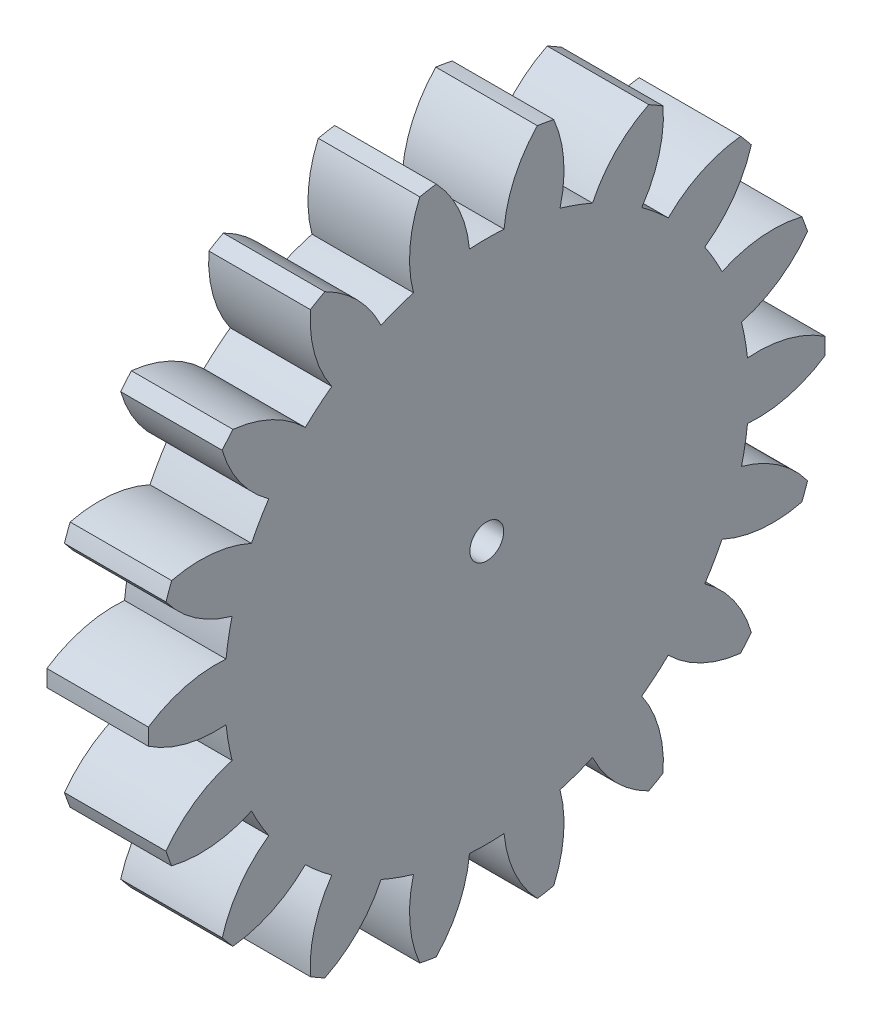
SolidWorks part; units mm, degrees
ref_plane "Plane1" through (0, 0, 0) normal (0, 0, 1) x (1, 0, 0)
ref_plane "Plane2" through (0, 0, 0) normal (0, 1, 0) x (1, 0, 0)
ref_plane "Plane3" through (0, 0, 0) normal (1, 0, 0) x (0, 0, -1)
sketch "HoldingSke" plane through (0, 0, 0) normal (0, 1, 0) x (1, 0, 0)
  line L0 (0, 0) -> (0.9511, -0.309)
  line L1 (-15, 0) -> (100, 0) construction
  line L2 (0, 0) -> (-2.1039, 2.3779)
  line L3 (0, 0) -> (-11.863, 4.5341)
  line L4 (0, 0) -> (8.2133, 2.6687)
  line L5 (0, 0) -> (-46.8476, -17.4728)
  line L6 (0, 0) -> (-2.4869, -1.6779)
  line L7 (-2.1039, 2.3779) -> (8.6586, 51.2059)
  line L8 (-76.2, 54.61) -> (-76.1, 54.61)
  line L9 (-71.009, 38.7566) -> (-53.1078, 45.2721)
  line L10 (-76.2, 71.12) -> (104.1128, 71.12)
  line L11 (0, 0) -> (-3, 0)
  line L12 (-76.2, 101.6) -> (-76.162, 101.6)
  line L13 (24.9733, 27.94) -> (52.9518, 28.4284)
  line L14 (24.9733, 27.94) -> (24.9743, 27.94)
  line L15 (24.9733, 27.94) -> (100.4006, 29.5858)
  line L16 (-63.627, -1) -> (-12.827, -1)
  circle A0 centre (0, 0) radius 0.5
  circle A1 centre (0, 0) radius 7.749
  circle A2 centre (0, 0) radius 37.5
  circle A3 centre (0, 0) radius 0.5
  dimension "Num_teeth" = 18
  dimension "Pitch_radius" = 180.3128
  dimension "Width" = 3
  dimension "Thickness" = 3
sketch "BasProSke" plane through (0, 0, 0) normal (0, 1, 0) x (1, 0, 0)
  line L0 (-10, 0) -> (60, 0) construction
  line L1 (0, 0) -> (0, 10)
  line L2 (0, 0) -> (3, 0)
  line L3 (3, 0) -> (3, 10)
  line L4 (3, 10) -> (0, 10)
  dimension "Thickness" = 3
  dimension "Diameter" = 20
revolve "Base-Revolve" add sketch "BasProSke" angle 360 about L0
sketch "TooCutSke" plane through (0, 0, 0) normal (1, 0, 0) x (0, 0, -1)
  line L1 (0, 0) -> (0, 107) construction
  line L2 (0, 0) -> (-0.8509, 8.9597) construction
  line L3 (0, 0) -> (-3.1157, 17.6701) construction
  line L4 (-0.8509, 8.9597) -> (-1.5579, 8.835) construction
  arc A0 (0.5106, 7.7322) -> (-0.5106, 7.7322) centre (0, 0) ccw
  arc A1 (1.5152, 9.9102) -> (-1.5152, 9.9102) centre (0, 0) ccw
  circle A2 centre (0, 0) radius 9 construction
  circle A3 centre (0, 0) radius 8.4572 construction
  arc A4 (-0.5106, 7.7322) -> (-1.5152, 9.9102) centre (-4.0952, 7.3996) ccw
  arc A5 (1.5152, 9.9102) -> (0.5106, 7.7322) centre (4.0952, 7.3996) ccw
extrude "ToothCut" cut sketch "TooCutSke" along normal through all
fillet "Breaks" [suppressed] radius 0.02 tangent propagation no
fillet "RootFillets" [suppressed] radius 0.251
pattern_circular "TeethCuts" count 18 every 20 about axis through (-10, 0, 0) along (1, 0, 0) of "ToothCut", "RootFillets", "Breaks"
sketch "HubNeaOneSke" plane through (0, 0, 0) normal (-1, 0, 0) x (0, 0, 1)
  circle A0 centre (0, 0) radius 7.749
  dimension "Diameter" = 15.498
extrude "HubNearOne" [suppressed] add sketch "HubNeaOneSke" along normal blind 47.0001
sketch "HubNeaBotSke" plane through (0, 0, 0) normal (-1, 0, 0) x (0, 0, 1)
  circle A0 centre (0, 0) radius 7.749
  dimension "Diameter" = 15.498
extrude "HubNearBoth" [suppressed] add sketch "HubNeaBotSke" along normal blind 23.5
ref_plane "FarPln" through (3, 0, 0) normal (1, 0, 0) x (0, 0, -1)
sketch "HubFarSke" plane through (3, 0, 0) normal (1, 0, 0) x (0, 0, -1)
  circle A0 centre (0, 0) radius 7.749
  dimension "Diameter" = 15.498
extrude "HubFar" [suppressed] add sketch "HubFarSke" along normal blind 23.5
sketch "BorSke" plane through (0, 0, 0) normal (1, 0, 0) x (0, 0, -1)
  circle A0 centre (0, 0) radius 0.5
  dimension "Diameter" = 1
extrude "Bore" cut sketch "BorSke" along normal mid plane 100.0001
sketch "KeySke" plane through (0, 0, 0) normal (1, 0, 0) x (0, 0, -1)
  line L0 (-0.05, 0) -> (-0.05, 0.6)
  line L1 (-0.05, 0.6) -> (0.05, 0.6)
  line L2 (0.05, 0.6) -> (0.05, 0)
  line L3 (0, 0) -> (0, 34) construction
  line L4 (-0.05, 0) -> (0.05, 0)
extrude "Keyway" [suppressed] cut sketch "KeySke" along normal mid plane 100.0001
pattern_circular "Keyway2" [suppressed] count 2 every 90 about axis through (-10, 0, 0) along (1, 0, 0) reverse direction yes
equation "' \"Module@HoldingSke\" = 6.35"
equation "' \"Num_teeth@HoldingSke\" = 12"
equation "' \"Ap@HoldingSke\" =  20"
equation "' \"Ap@HoldingSke\" = 20"
equation "' \"Width@HoldingSke\" = 0.5 * 25.4"
equation "' \"Hub_dia@HoldingSke\"= 1 * 25.4"
equation "' \"Hub_dia@HoldingSke\" = 1 * 25.4"
equation "' \"Overall_len@HoldingSke\" = 1.0 * 25.4"
equation "' \"Bore@HoldingSke\" = 0.75 * 25.4"
equation "' \"T_dim@HoldingSke\" = 0.1 * 25.4"
equation "' \"Width@KeySke\" = 0.25 * 25.4"
equation "' \"Show_teeth@HoldingSke\" = 13"
equation "' \"Backlash@HoldingSke\" = 0.009 * 25.4"
equation "' \"Addendum_fac@HoldingSke\" = 1.0"
equation "' \"Dedendum_fac@HoldingSke\" = 1.25"
equation "' \"Dedendum_add@HoldingSke\" = 0.00005 * 25.4"
equation "' \"Clearance_fac@HoldingSke\" = 0.25"
equation "\"Pitch@HoldingSke\" = 1 / \"Module@HoldingSke\""
equation "\"Overcut_dia@TooCutSke\" = (\"Num_teeth@HoldingSke\" + 2 * \"Addendum_fac@HoldingSke\") / \"Pitch@HoldingSke\" + 0.002 * 25.4"
equation "\"Pitch_dia@TooCutSke\" = \"Num_teeth@HoldingSke\" / \"Pitch@HoldingSke\""
equation "\"Base_dia@TooCutSke\" = \"Num_teeth@HoldingSke\" / \"Pitch@HoldingSke\" * cos((\"Ap@HoldingSke\"  * 3.14159265 / 180))"
equation "\"Root_dia@TooCutSke\" = (\"Num_teeth@HoldingSke\" + 2) / \"Pitch@HoldingSke\" - 2 * (\"Addendum_fac@HoldingSke\" + \"Dedendum_fac@HoldingSke\") / \"Pitch@HoldingSke\" - \"Dedendum_add@HoldingSke\" * 2"
equation "\"Half_ang@TooCutSke\" = 180 / \"Num_teeth@HoldingSke\""
equation "\"Half_CT@TooCutSke\" = \"Num_teeth@HoldingSke\" / \"Pitch@HoldingSke\" * sin((3.14159265 / 2 / \"Num_teeth@HoldingSke\")) / 2 - 7 * \"Backlash@HoldingSke\" / 4"
equation "\"Flank_rad@TooCutSke\" = \"Num_teeth@HoldingSke\" / \"Pitch@HoldingSke\" / 5"
equation "\"Radius@RootFillets\" = \"Clearance_fac@HoldingSke\" / \"Pitch@HoldingSke\" + \"Dedendum_add@HoldingSke\""
equation "\"Break_rad@Breaks\" = 0.02 / \"Pitch@HoldingSke\""
equation "\"Thickness@HoldingSke\" = \"Width@HoldingSke\""
equation "\"OAL@HoldingSke\" = \"Thickness@HoldingSke\""
equation "\"MHD@HoldingSke\" = (\"Num_teeth@HoldingSke\" + 2) / \"Pitch@HoldingSke\" - 2 * (\"Addendum_fac@HoldingSke\" + \"Dedendum_fac@HoldingSke\")  / \"Pitch@HoldingSke\" - \"Dedendum_add@HoldingSke\" * 2"
equation "\"MBD@HoldingSke\" = (\"Num_teeth@HoldingSke\" + 2) / \"Pitch@HoldingSke\" - 2 * (\"Addendum_fac@HoldingSke\" + \"Dedendum_fac@HoldingSke\")  / \"Pitch@HoldingSke\" - \"Dedendum_add@HoldingSke\" * 2 - 0.002 * 25.4"
equation "\"MHD@HoldingSke\" = ((sgn( \"MHD@HoldingSke\" - \"Hub_dia@HoldingSke\" )-1)*( \"MHD@HoldingSke\" - \"Hub_dia@HoldingSke\" ))/-2+ \"Hub_dia@HoldingSke\""
equation "\"MBD@HoldingSke\" = ((sgn( \"MBD@HoldingSke\" - \"Bore@HoldingSke\" )-1)*( \"MBD@HoldingSke\" - \"Bore@HoldingSke\" ))/-2+ \"Bore@HoldingSke\""
equation "\"OAL@HoldingSke\" = ((sgn( \"OAL@HoldingSke\" - \"Overall_len@HoldingSke\" )+1)*( \"OAL@HoldingSke\" - \"Overall_len@HoldingSke\" ))/2 + \"Overall_len@HoldingSke\" + 0.000002 * 25.4"
equation "\"Num_teeth@TeethCuts\" = int( \"Show_teeth@HoldingSke\" ) + 1"
equation "\"Num_teeth@TeethCuts\" = ((sgn( \"Num_teeth@TeethCuts\" - \"Num_teeth@HoldingSke\" )-1)*( \"Num_teeth@TeethCuts\" - \"Num_teeth@HoldingSke\" ))/-2+ \"Num_teeth@HoldingSke\""
equation "\"Num_teeth@TeethCuts\" = ((sgn( \"Num_teeth@TeethCuts\" - 2.0)+1)*( \"Num_teeth@TeethCuts\" - 2.0))/2 +2.0"
equation "\"Angle@TeethCuts\" = 360.0 / \"Num_teeth@HoldingSke\""
equation "\"Diameter@BasProSke\" = (\"Num_teeth@HoldingSke\" + 2 * \"Addendum_fac@HoldingSke\") / \"Pitch@HoldingSke\""
equation "\"Thickness@BasProSke\"  = \"Thickness@HoldingSke\""
equation "' \"Fillet_rad@BasProSke\" =  \"Thickness@HoldingSke\" * 0.05"
equation "' \"Fillet_rad@BasProSke\" = \"Thickness@HoldingSke\" * 0.05"
equation "\"MHD@HoldingSke\" = ((sgn( \"MHD@HoldingSke\" - \"Root_dia@TooCutSke\" )-1)*( \"MHD@HoldingSke\" - \"Root_dia@TooCutSke\" ))/-2+ \"Root_dia@TooCutSke\""
equation "\"Diameter@HubNeaOneSke\" = \"MHD@HoldingSke\""
equation "\"Length@HubNearOne\" = \"OAL@HoldingSke\" - \"Thickness@BasProSke\""
equation "\"Diameter@HubNeaBotSke\" = \"MHD@HoldingSke\""
equation "\"Length@HubNearBoth\" = ( \"OAL@HoldingSke\" - \"Thickness@BasProSke\" ) / 2.0"
equation "\"Thickness@FarPln\" = \"Thickness@BasProSke\""
equation "\"Diameter@HubFarSke\" = \"MHD@HoldingSke\""
equation "\"Length@HubFar\" = ( \"OAL@HoldingSke\" - \"Thickness@BasProSke\" ) / 2.0"
equation "\"Diameter@BorSke\" = \"MBD@HoldingSke\""
equation "\"D1@Bore\" = \"OAL@HoldingSke\" * 2.0"
equation "\"D1@Keyway\" = \"OAL@HoldingSke\" * 2.0"
equation "\"Offset@KeySke\" = \"T_dim@HoldingSke\" + \"MBD@HoldingSke\" / 2.0"
